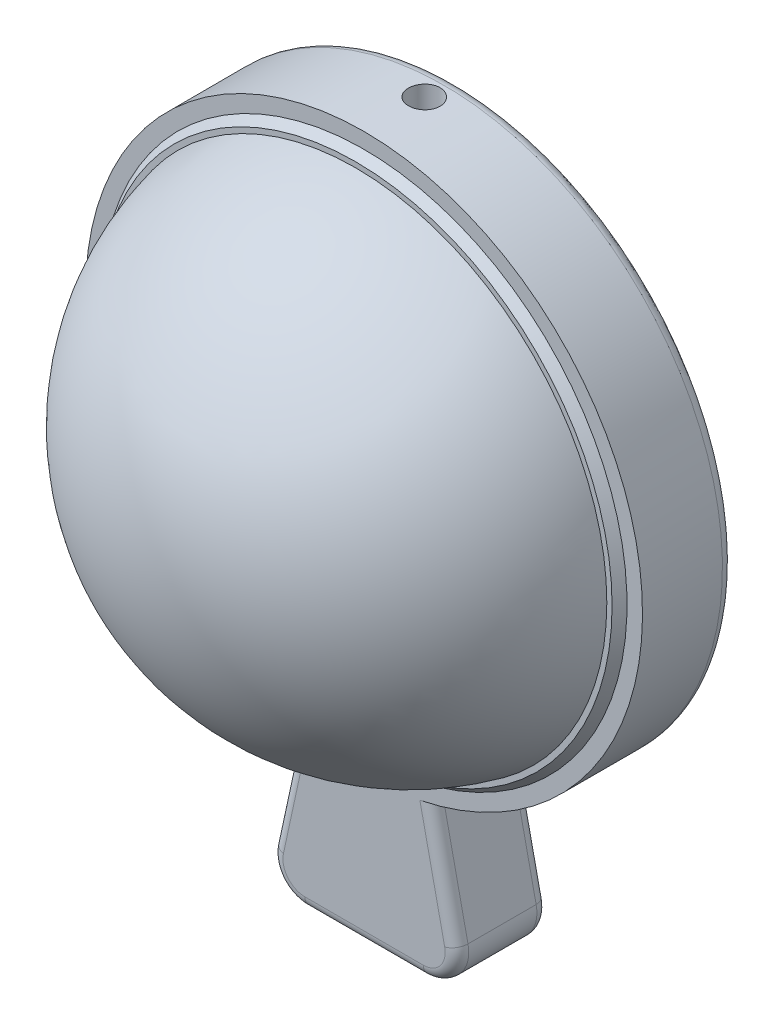
SolidWorks part; units mm, degrees
material "201 Annealed Stainless Steel (SS)"
ref_plane "Front Plane" through (0, 0, 0) normal (0, 0, 1) x (1, 0, 0)
ref_plane "Top Plane" through (0, 0, 0) normal (0, 1, 0) x (1, 0, 0)
ref_plane "Right Plane" through (0, 0, 0) normal (1, 0, 0) x (0, 0, -1)
sketch "Sketch1" plane through (0, 0, 0) normal (0, 1, 0) x (1, 0, 0)
  line L0 (-11.7633, 21.1857) -> (-11.7633, 7.3427)
  line L1 (-11.7633, 7.3427) -> (-14.1001, 7.3427)
  line L2 (-14.1001, 7.3427) -> (-15.0843, 6.0727)
  line L3 (-15.0843, 6.0727) -> (-15.8781, 6.0727)
  line L4 (-11.7633, 21.1857) -> (-53.7876, 21.1857)
  line L5 (-53.7876, 21.1857) -> (-53.7876, -24.5343)
  arc A0 (-53.7876, -24.5343) -> (-15.8781, 6.0727) centre (-53.7876, 14.2464) ccw
  dimension "D8" = 38.7806
  dimension "D1" = 42.0243
  dimension "D2" = 13.843
  dimension "D3" = 15.113
  dimension "D4" = 39.6875
  dimension "D5" = 37.9095
  dimension "D6" = 0.7937
  dimension "D7" = 45.72
revolve "Revolve1" add sketch "Sketch1" angle 360 about L5
shell "Shell1" thickness 4.7625 removed face at (-95.8119, 0, -21.1857)
sketch "Sketch5" plane through (0, 0, -21.1857) normal (0, 0, -1) x (-1, 0, 0)
  line L0 (53.7876, 0) -> (53.7876, 50000) construction
  line L5 (53.7876, -42.0243) -> (63.9476, -40.7776)
  line L6 (63.9476, -40.7776) -> (69.0276, -64.2493)
  line L7 (69.0276, -64.2493) -> (38.5476, -64.2493)
  line L8 (53.7876, -64.2493) -> (53.7876, -42.0243)
  line L9 (53.7876, -42.0243) -> (43.6276, -40.7776)
  line L10 (43.6276, -40.7776) -> (38.5476, -64.2493)
  circle A0 centre (53.7876, 0) radius 42.0243 construction
  circle M15 centre (53.7876, 0) radius 42.0243
  dimension "D1" = 10.16
  dimension "D2" = 22.225
  dimension "D3" = 15.24
extrude "Boss-Extrude1" add sketch "Sketch5" along direction (0, 0, -1) on the side against the normal up to surface (13.843 mm away) contours L10 L7 L8 M15 | L8 L7 L6 M15 region at (-60.2988, -53.6473, -21.1857) region at (-47.2764, -53.6473, -21.1857) up to face at (-95.8119, 0, -7.3427)
sketch "Sketch2" plane through (0, 0, 0) normal (0, 1, 0) x (1, 0, 0)
  line L0 (-95.8119, 21.1857) -> (-11.7633, 21.1857) construction
  line L1 (-11.7633, 7.3427) -> (-11.7633, 21.1857) construction
  line L2 (-11.7633, 21.1857) -> (-95.8119, 21.1857) construction
  circle A0 centre (-53.7876, 16.4232) radius 2.3812
  point P9 (-53.7876, 21.1857)
  dimension "D1" = 4.7625
  dimension "D2" = 4.7625
extrude "Cut-Extrude1" cut sketch "Sketch2" against normal through all and the other way through all
fillet "Fillet1" radius 5.08 2 edges at (-38.5476, -64.2493, -14.2642) (-69.0276, -64.2493, -14.2642)
fillet "Fillet2" radius 1.778 12 edges at (-65.8216, -49.4362, -7.3427) (-66.6843, -62.3589, -7.3427) (-53.7876, -64.2493, -7.3427) (-16.5258, 0, -21.1857) (-40.8909, -62.3589, -7.3427) (-41.7536, -49.4362, -7.3427) (-66.6843, -62.3589, -21.1857) (-65.8216, -49.4362, -21.1857) (-53.7876, -64.2493, -21.1857) (-40.8909, -62.3589, -21.1857) (-41.7536, -49.4362, -21.1857) (-53.7876, 42.0243, -21.1857)
